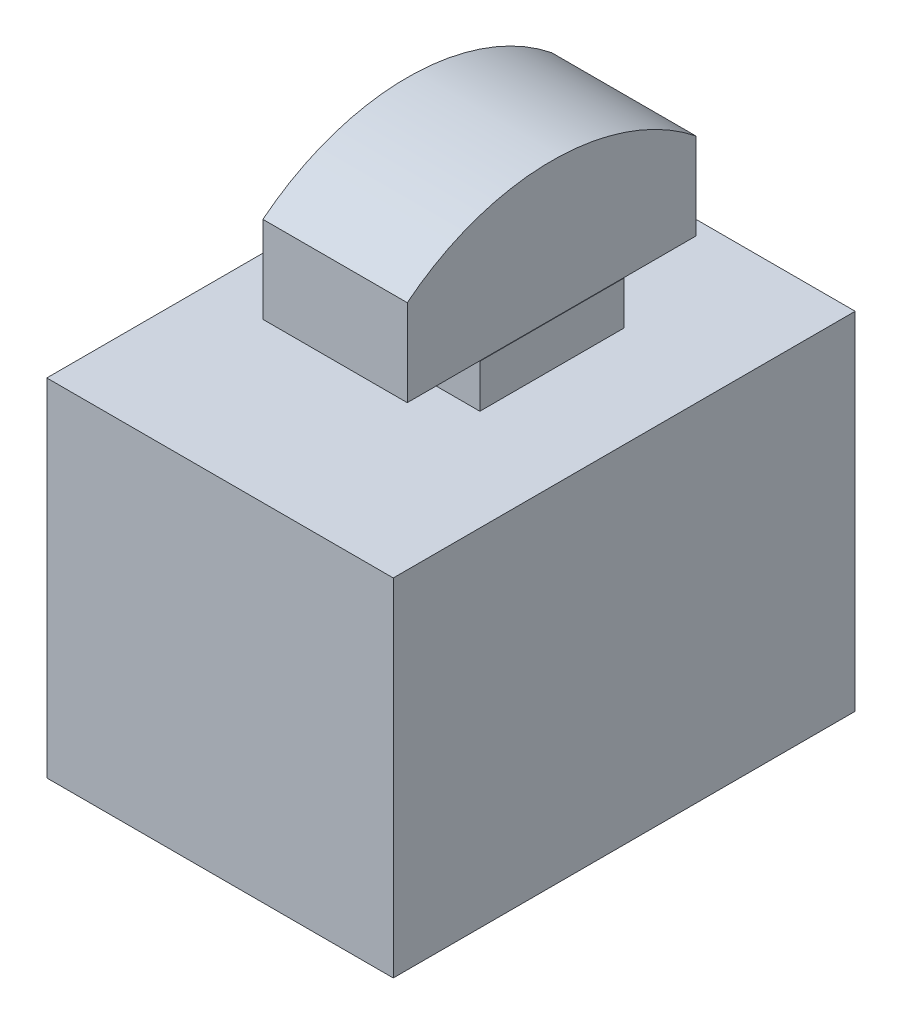
SolidWorks part; units mm, degrees
ref_plane "정면" through (0, 0, 0) normal (0, 0, 1) x (1, 0, 0)
ref_plane "윗면" through (0, 0, 0) normal (0, 1, 0) x (1, 0, 0)
ref_plane "우측면" through (0, 0, 0) normal (1, 0, 0) x (0, 0, -1)
sketch "스케치1" plane through (0, 0, 0) normal (0, 0, 1) x (1, 0, 0)
  line L1 (-6, 6) -> (6, 6)
  line L2 (-6, 6) -> (-6, -6)
  line L3 (-6, -6) -> (6, -6)
  line L4 (6, 6) -> (6, -6)
  line L5 (-6, 6) -> (6, -6) construction
  line L6 (-6, -6) -> (6, 6) construction
  point P0 (0, 0)
  dimension "D1" = 12
  dimension "D2" = 12
extrude "보스-돌출1" add sketch "스케치1" along normal blind 16
sketch "스케치2" plane through (0, 6, 0) normal (0, 1, 0) x (1, 0, 0)
  line L0 (6, 0) -> (-6, 0) construction
  line L1 (-2.5, -4.5) -> (2.5, -4.5)
  line L2 (-2.5, -4.5) -> (-2.5, -9.5)
  line L3 (-2.5, -9.5) -> (2.5, -9.5)
  line L4 (2.5, -4.5) -> (2.5, -9.5)
  line L5 (-2.5, -4.5) -> (2.5, -9.5) construction
  line L6 (-2.5, -9.5) -> (2.5, -4.5) construction
  line L7 (-6, -16) -> (-6, 0) construction
  point P0 (0, -7)
  dimension "D1" = 7
  dimension "D2" = 5
  dimension "D3" = 5
  dimension "D4" = 6
extrude "보스-돌출2" add sketch "스케치2" along normal blind 1.5
sketch "스케치3" plane through (0, 7.5, 0) normal (0, 1, 0) x (1, 0, 0)
  line L0 (6, 0) -> (-6, 0) construction
  line L1 (-2.515, -2) -> (2.485, -2)
  line L2 (-2.515, -2) -> (-2.515, -12)
  line L3 (-2.515, -12) -> (2.485, -12)
  line L4 (2.485, -2) -> (2.485, -12)
  line L5 (-2.515, -2) -> (2.485, -12) construction
  line L6 (-2.515, -12) -> (2.485, -2) construction
  point P0 (-0.015, -7)
  dimension "D1" = 2
  dimension "D2" = 5
  dimension "D3" = 2.5
extrude "보스-돌출3" add sketch "스케치3" along normal blind 3
sketch "스케치4" plane through (-2.515, 0, 0) normal (-1, 0, 0) x (0, 0, 1)
  line L0 (2, 10.5) -> (12, 10.5)
  arc A0 (2, 10.5) -> (12, 10.5) centre (7, 4.255) cw
  dimension "D1" = 8
extrude "보스-돌출4" add sketch "스케치4" against normal up to surface (5 mm away) up to face at (2.485, 8.5, 7)
